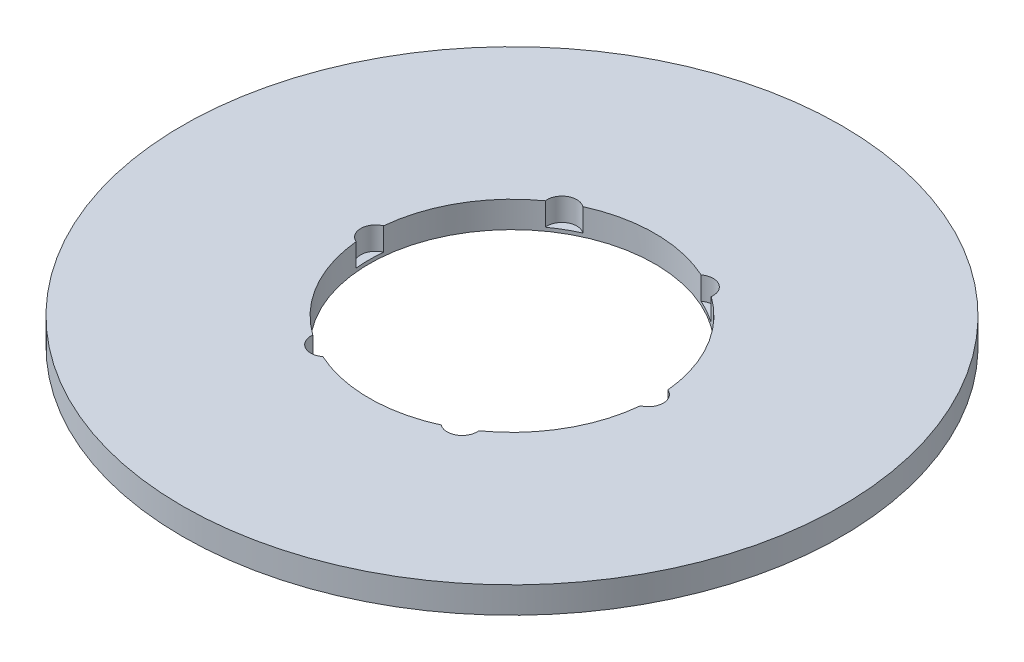
SolidWorks part; units mm, degrees
ref_plane "Front Plane" through (0, 0, 0) normal (0, 0, 1) x (1, 0, 0)
ref_plane "Top Plane" through (0, 0, 0) normal (0, 1, 0) x (1, 0, 0)
ref_plane "Right Plane" through (0, 0, 0) normal (1, 0, 0) x (0, 0, -1)
sketch "Sketch1" plane through (0, 0, 0) normal (0, 1, 0) x (1, 0, 0)
  circle A0 centre (0, 0) radius 75
  dimension "FLANGE_OD" = 150
extrude "Boss-Extrude1" add sketch "Sketch1" along normal blind 6
sketch "Sketch2" plane through (0, 0, 0) normal (0, 1, 0) x (1, 0, 0)
  circle A0 centre (0, 0) radius 32.5
  dimension "BORE_D" = 65
extrude "Cut-Extrude1" cut sketch "Sketch2" along normal through all
sketch "Sketch3" plane through (0, 6, 0) normal (0, 1, 0) x (1, 0, 0)
  circle A0 centre (0, 0) radius 31.0349 construction
  circle A1 centre (-31.0349, 0) radius 3.3907
  dimension "BOLT_D" = 6.7815
  dimension "BOLT_PCD" = 62.0697
extrude "Cut-Extrude2" cut sketch "Sketch3" against normal blind 5.2047
pattern_circular "CirPattern1" count 6 over 360 about axis through (0, 0, 0) along (0, 1, 0) of "Cut-Extrude2"
